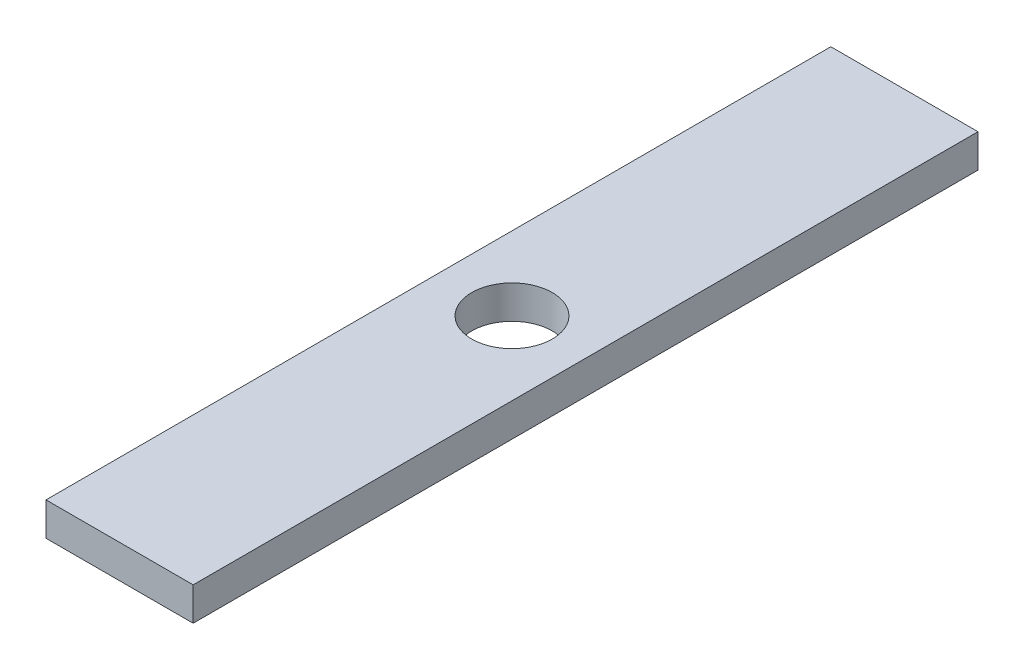
SolidWorks part; units mm, degrees
ref_plane "前视基准面" through (0, 0, 0) normal (0, 0, 1) x (1, 0, 0)
ref_plane "上视基准面" through (0, 0, 0) normal (0, 1, 0) x (1, 0, 0)
ref_plane "右视基准面" through (0, 0, 0) normal (1, 0, 0) x (0, 0, -1)
sketch "草图1" plane through (0, 0, 0) normal (0, 1, 0) x (1, 0, 0)
  line L1 (0, 0) -> (42, 0)
  line L2 (0, 0) -> (0, -224)
  line L3 (0, -224) -> (42, -224)
  line L4 (42, 0) -> (42, -224)
  dimension "D1" = 42
  dimension "D2" = 224
extrude "凸台-拉伸1" add sketch "草图1" along normal blind 9.5
sketch "草图2" plane through (0, 9.5, 0) normal (0, 1, 0) x (1, 0, 0)
  line L0 (0, -112) -> (42, -112) construction
  line L1 (0, 0) -> (0, -224) construction
  line L2 (42, -224) -> (42, 0) construction
  line L3 (21, 0) -> (21, -224) construction
  line L4 (42, 0) -> (0, 0) construction
  line L5 (0, -224) -> (42, -224) construction
  circle A0 centre (21, -112) radius 11.5
  dimension "D1" = 23
extrude "切除-拉伸1" cut sketch "草图2" against normal through all
